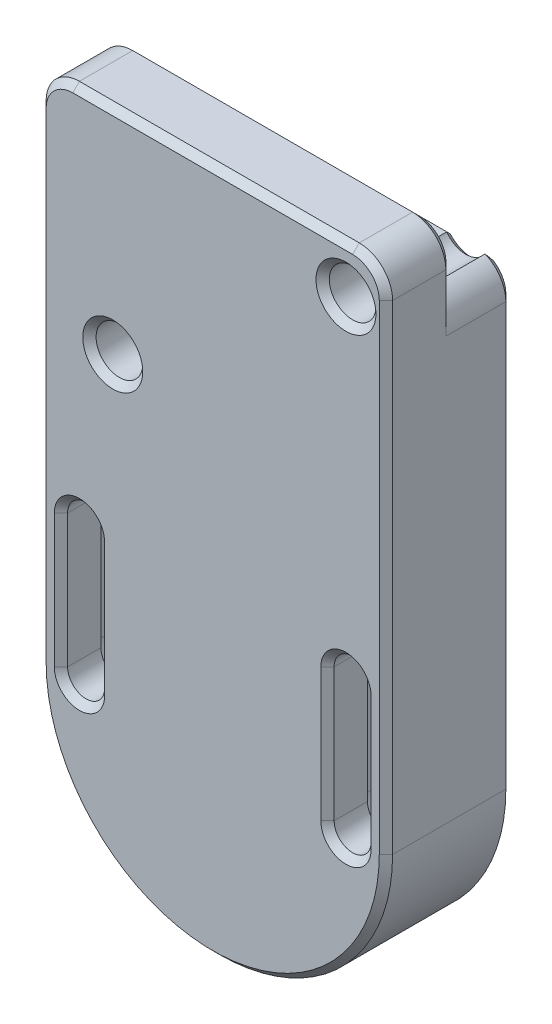
SolidWorks part; units mm, degrees
ref_plane "Front Plane" through (0, 0, 0) normal (0, 0, 1) x (1, 0, 0)
ref_plane "Top Plane" through (0, 0, 0) normal (0, 1, 0) x (1, 0, 0)
ref_plane "Right Plane" through (0, 0, 0) normal (1, 0, 0) x (0, 0, -1)
sketch "Sketch1" plane through (0, 0, 0) normal (0, 0, 1) x (1, 0, 0)
  line L0 (210, 74) -> (300, 74) construction
  line L1 (210, 300) -> (210, 74) construction
  line L2 (210, 74) -> (300, 74)
  line L3 (210, 300) -> (210, 74)
  line L4 (261, 71) -> (260, 71)
  line L5 (255, 71) -> (210, 71)
  line L6 (209, 71) -> (209, 41)
  line L7 (209, 41) -> (209, -59)
  line L8 (210, -59) -> (260, -59)
  line L9 (255, 71) -> (260, 71)
  line L10 (261, 71) -> (261, -59)
  line L11 (210, 71) -> (209, 71)
  line L12 (210, -59) -> (209, -59)
  line L13 (261, -59) -> (260, -59)
  circle A4 centre (255, 64) radius 3.5
  circle A5 centre (220, 39) radius 3.5
extrude "Boss-Extrude1" add sketch "Sketch1" along normal blind 19 contours L10 L9 L5 L6 L7 L8 A5 A4 region at (234.9712, 5.476, 0)
sketch "Sketch2" plane through (0, 0, 19) normal (0, 0, 1) x (1, 0, 0)
  line L0 (209, 71) -> (209, -59) construction
  line L1 (209, -59) -> (261, -59) construction
  line L2 (261, 71) -> (261, -59) construction
  line L4 (209, -59) -> (261, -59)
  line L6 (209, -6) -> (209, -59)
  line L7 (261, -6) -> (261, -59)
  arc A0 (209, -6) -> (261, -6) centre (235, -6) ccw
extrude "Cut-Extrude1" cut sketch "Sketch2" against normal through all
sketch "Sketch3" plane through (0, 0, 19) normal (0, 0, 1) x (1, 0, 0)
  line L4 (212.225, 14) -> (212.225, -6)
  line L5 (217.775, 14) -> (217.775, -6)
  line L6 (252.225, 14) -> (252.225, -6)
  line L7 (257.775, 14) -> (257.775, -6)
  arc A0 (252.225, -6) -> (257.775, -6) centre (255, -6) ccw
  arc A6 (212.225, -6) -> (217.775, -6) centre (215, -6) ccw
  arc A7 (217.775, 14) -> (212.225, 14) centre (215, 14) ccw
  arc A8 (257.775, 14) -> (252.225, 14) centre (255, 14) ccw
extrude "Cut-Extrude2" cut sketch "Sketch3" against normal through all
sketch "Sketch4" plane through (0, 0, 0) normal (0, 0, -1) x (-1, 0, 0)
  line L0 (-251, 14) -> (-251, -6)
  line L1 (-259, 14) -> (-259, -6)
  line L2 (-219, 14) -> (-219, -6)
  line L3 (-211, 14) -> (-211, -6)
  arc A0 (-251, 14) -> (-259, 14) centre (-255, 14) ccw
  arc A1 (-259, -6) -> (-251, -6) centre (-255, -6) ccw
  arc A2 (-219, -6) -> (-211, -6) centre (-215, -6) ccw
  arc A3 (-211, 14) -> (-219, 14) centre (-215, 14) ccw
extrude "Cut-Extrude3" cut sketch "Sketch4" against normal offset from surface (13 mm away) 6 up to face at (255, 4, 19)
sketch "Sketch5" plane through (261, 0, 0) normal (1, 0, 0) x (0, 0, -1)
  line L1 (0, 71) -> (-9, 71)
  line L2 (0, 71) -> (0, 62)
  line L3 (0, 62) -> (-9, 62)
  line L4 (-9, 71) -> (-9, 62)
extrude "Cut-Extrude4" cut sketch "Sketch5" against normal through all
fillet "Fillet1" radius 5 4 edges at (209, 71, 14) (261, 71, 14) (209, 62, 4.5) (261, 62, 4.5)
chamfer "Chamfer1" distance 1 angle 45 37 edges at (235, -32, 0) (261, 25.6819, 0) (209, 25.5, 0) (255, 60.5, 0) (223.5, 39, 0) (215, -10, 0) (211, 4, 0) (215, 18, 0) (219, 4, 0) (255, -10, 0) (251, 4, 0) (255, 18, 0) (259, 4, 0) (258.5, 64, 19) (223.5, 39, 19) (259.5355, 69.5355, 19) (261, 30, 19) (235, -32, 19) (209, 30, 19) (210.4645, 69.5355, 19) (235, 71, 19) (233.0639, 62, 0) (209, 61.5, 9) (261, 61.6819, 9) (210.4645, 69.5355, 9) (259.5355, 69.5355, 9) (235, 71, 9) (260.145, 60.1601, 0) (210.4645, 60.5355, 0) (212.225, 4, 19) (215, -8.775, 19) (217.775, 4, 19) (215, 16.775, 19) (252.225, 4, 19) (255, -8.775, 19) (257.775, 4, 19) (255, 16.775, 19)
